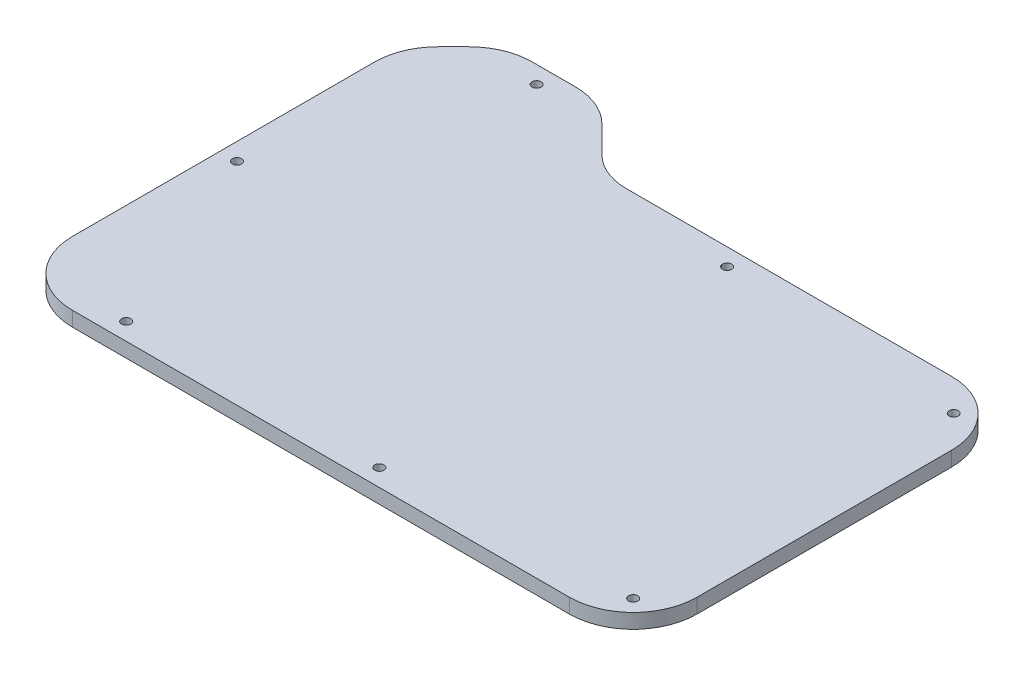
SolidWorks part; units mm, degrees
ref_plane "Front Plane" through (0, 0, 0) normal (0, 0, 1) x (1, 0, 0)
ref_plane "Top Plane" through (0, 0, 0) normal (0, 1, 0) x (1, 0, 0)
ref_plane "Right Plane" through (0, 0, 0) normal (1, 0, 0) x (0, 0, -1)
sketch "Sketch1" plane through (0, 0, 0) normal (0, 1, 0) x (1, 0, 0)
  line L30 (-37.2211, -95.1196) -> (-37.2211, -39.8196)
  line L31 (-51.0711, -25.9696) -> (-121.754, -25.9696)
  line L32 (-130.7342, -22.2498) -> (-136.5579, -16.4261)
  line L33 (-146.3513, -12.3696) -> (-155.7143, -12.3696)
  line L34 (-165.5078, -16.4261) -> (-168.788, -19.7064)
  line L35 (-172.8446, -29.4998) -> (-172.8446, -95.1196)
  line L36 (-158.9946, -108.9696) -> (-51.0711, -108.9696)
  arc A50 (-51.0711, -108.9696) -> (-37.2211, -95.1196) centre (-51.0711, -95.1196) ccw
  arc A51 (-37.2211, -39.8196) -> (-51.0711, -25.9696) centre (-51.0711, -39.8196) ccw
  arc A52 (-130.7342, -22.2498) -> (-121.754, -25.9696) centre (-121.754, -13.2696) ccw
  arc A53 (-136.5579, -16.4261) -> (-146.3513, -12.3696) centre (-146.3513, -26.2196) ccw
  arc A54 (-155.7143, -12.3696) -> (-165.5078, -16.4261) centre (-155.7143, -26.2196) ccw
  arc A55 (-168.788, -19.7064) -> (-172.8446, -29.4998) centre (-158.9946, -29.4998) ccw
  arc A56 (-172.8446, -95.1196) -> (-158.9946, -108.9696) centre (-158.9946, -95.1196) ccw
  circle A57 centre (-169.0946, -63.1097) radius 1
  circle A58 centre (-151.0328, -16.1196) radius 1
  circle A59 centre (-96.0754, -29.7196) radius 1
  circle A60 centre (-43.9293, -32.6778) radius 1
  circle A61 centre (-43.9293, -102.2613) radius 1
  circle A62 centre (-96.0754, -105.2196) radius 1
  circle A63 centre (-151.0328, -105.2196) radius 1
extrude "Boss-Extrude1" add sketch "Sketch1" along normal blind 3.175
